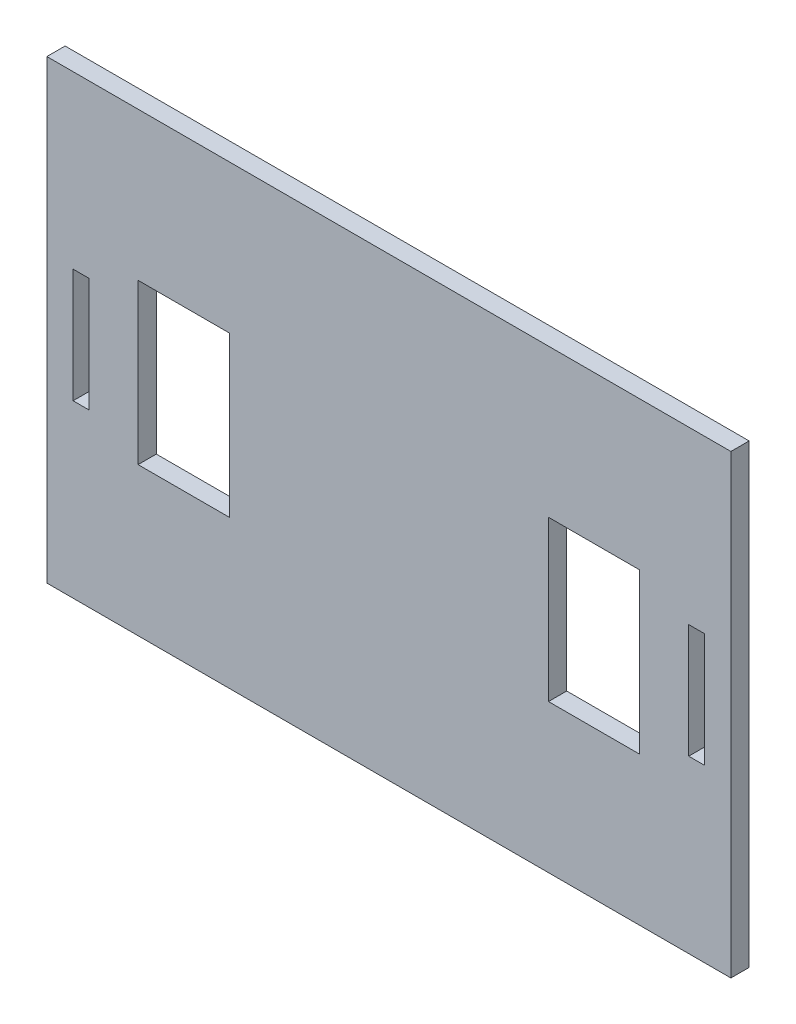
SolidWorks part; units mm, degrees
ref_plane "Front" through (0, 0, 0) normal (0, 0, 1) x (1, 0, 0)
ref_plane "Top" through (0, 0, 0) normal (0, 1, 0) x (1, 0, 0)
ref_plane "Right" through (0, 0, 0) normal (1, 0, 0) x (0, 0, -1)
sketch "Esquisse1" plane through (0, 0, 0) normal (0, 0, 1) x (1, 0, 0)
  line L1 (0, 0) -> (300, 0)
  line L2 (0, 0) -> (0, 200)
  line L3 (0, 200) -> (300, 200)
  line L4 (300, 0) -> (300, 200)
  dimension "D1" = 300
  dimension "D2" = 200
extrude "Boss.-Extru.1" add sketch "Esquisse1" along normal blind 8
sketch "Esquisse2" plane through (0, 0, 8) normal (0, 0, 1) x (1, 0, 0)
  line L0 (150, 200) -> (150, 0) construction
  line L1 (40, 65) -> (80, 65)
  line L2 (40, 65) -> (40, 135)
  line L3 (40, 135) -> (80, 135)
  line L4 (80, 65) -> (80, 135)
  line L5 (300, 200) -> (0, 200) construction
  line L6 (0, 0) -> (300, 0) construction
  line L7 (80, 100) -> (150, 100) construction
  line L8 (60, 65) -> (60, 135) construction
  line L9 (40, 100) -> (18.5, 100) construction
  line L10 (15, 75) -> (15, 125) construction
  line L11 (11.5, 75) -> (18.5, 75)
  line L12 (11.5, 75) -> (11.5, 125)
  line L13 (11.5, 125) -> (18.5, 125)
  line L14 (18.5, 75) -> (18.5, 125)
  line L15 (285, 75) -> (285, 125) construction
  line L16 (260, 100) -> (281.5, 100) construction
  line L17 (240, 65) -> (240, 135) construction
  line L18 (281.5, 75) -> (281.5, 125)
  line L19 (288.5, 125) -> (281.5, 125)
  line L20 (288.5, 75) -> (288.5, 125)
  line L21 (288.5, 75) -> (281.5, 75)
  line L22 (220, 65) -> (220, 135)
  line L23 (260, 135) -> (220, 135)
  line L24 (260, 65) -> (260, 135)
  line L25 (260, 65) -> (220, 65)
  dimension "D1" = 100
  dimension "D2" = 70
  dimension "D3" = 40
  dimension "D4" = 180
  dimension "D5" = 7
  dimension "D6" = 50
  dimension "D7" = 270
extrude "Enlèv. mat.-Extru.1" cut sketch "Esquisse2" against normal through all
